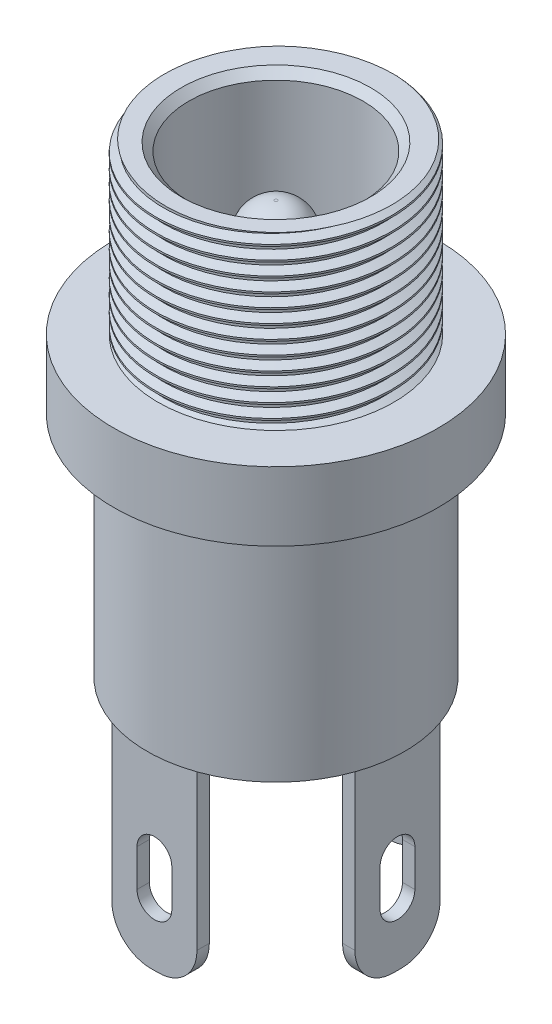
SolidWorks part; units mm, degrees
material "Chrome Stainless Steel"
ref_plane "Front" through (0, 0, 0) normal (0, 0, 1) x (1, 0, 0)
ref_plane "Top" through (0, 0, 0) normal (0, 1, 0) x (1, 0, 0)
ref_plane "Right" through (0, 0, 0) normal (1, 0, 0) x (0, 0, -1)
sketch "Sketch1" plane through (0, 0, 0) normal (0, 1, 0) x (1, 0, 0)
  circle A0 centre (0, 0) radius 3.8735
  circle A1 centre (0, 0) radius 2.8575
  dimension "D1" = 7.747
  dimension "D2" = 5.715
extrude "Boss-Extrude1" add sketch "Sketch1" along normal blind 5.461
chamfer "Chamfer1" distance 0.254 angle 45 1 edges at (0, 5.461, 2.8575)
sketch "Sketch2" plane through (0, 0, 0) normal (0, -1, 0) x (1, 0, 0)
  circle A0 centre (0, 0) radius 5.334
  dimension "D1" = 10.668
extrude "Boss-Extrude2" add sketch "Sketch2" along normal blind 2.2606
sketch "Sketch3" plane through (0, -2.2606, 0) normal (0, -1, 0) x (1, 0, 0)
  circle A0 centre (0, 0) radius 4.2291
  dimension "D1" = 8.4582
extrude "Boss-Extrude3" add sketch "Sketch3" along normal blind 7.493
sketch "Sketch4" plane through (0, 5.461, 0) normal (0, 1, 0) x (1, 0, 0)
  circle A0 centre (0, 0) radius 2.8575
extrude "Cut-Extrude1" cut sketch "Sketch4" against normal blind 11
sketch "Sketch5" plane through (0, -5.539, 0) normal (0, 1, 0) x (1, 0, 0)
  circle A0 centre (0, 0) radius 1.05
  dimension "D1" = 2.1
extrude "Boss-Extrude4" add sketch "Sketch5" along normal offset from surface (9.349 mm away) 1.651 up to face at (0, 5.461, 3.1115)
fillet "Fillet1" radius 1 1 edges at (0, 3.81, 1.05)
sketch "Sketch6" plane through (0, -9.7536, 0) normal (0, -1, 0) x (1, 0, 0)
  line L1 (-1.397, 3.9917) -> (1.397, 3.9917)
  line L2 (-1.397, 3.9917) -> (-1.397, 3.5853)
  line L3 (-1.397, 3.5853) -> (1.397, 3.5853)
  line L4 (1.397, 3.9917) -> (1.397, 3.5853)
  line L5 (3.5853, 1.397) -> (3.9917, 1.397)
  line L6 (3.5853, 1.397) -> (3.5853, -1.397)
  line L7 (3.5853, -1.397) -> (3.9917, -1.397)
  line L8 (3.9917, 1.397) -> (3.9917, -1.397)
  line L9 (1.397, -3.5853) -> (-1.397, -3.5853)
  line L10 (1.397, -3.5853) -> (1.397, -3.9917)
  line L11 (1.397, -3.9917) -> (-1.397, -3.9917)
  line L12 (-1.397, -3.5853) -> (-1.397, -3.9917)
  circle A0 centre (0, 0) radius 4.2291 construction
  circle A1 centre (0, 0) radius 4.2291 construction
  point P21 (0, -3.9917)
  point P23 (0, 3.9917)
  point P24 (3.9917, 0)
  dimension "D1" = 2.794
  dimension "D2" = 0.4064
extrude "Boss-Extrude5" add sketch "Sketch6" along normal blind 6.35
sketch "Sketch7" plane through (0, 0, 0) normal (1, 0, 0) x (0, 0, -1)
  line L0 (0, -12.8651) -> (0, -14.0843) construction
  line L1 (0.5715, -12.8651) -> (0.5715, -14.0843)
  line L2 (-0.5715, -12.8651) -> (-0.5715, -14.0843)
  line L3 (1.397, -16.1036) -> (-1.397, -16.1036) construction
  arc A0 (0.5715, -12.8651) -> (-0.5715, -12.8651) centre (0, -12.8651) ccw
  arc A1 (-0.5715, -14.0843) -> (0.5715, -14.0843) centre (0, -14.0843) ccw
  point P2 (0, -13.4747)
  point P7 (0, -12.2936)
  point P9 (0, -14.6558)
  dimension "D1" = 1.143
  dimension "D2" = 2.3622
  dimension "D3" = 1.4478
extrude "Cut-Extrude2" cut sketch "Sketch7" along normal through all
sketch "Sketch8" plane through (0, 0, 0) normal (0, 0, 1) x (1, 0, 0)
  line L0 (0, -12.8651) -> (0, -14.0843) construction
  line L1 (0.5715, -12.8651) -> (0.5715, -14.0843)
  line L2 (-0.5715, -12.8651) -> (-0.5715, -14.0843)
  arc A0 (0.5715, -12.8651) -> (-0.5715, -12.8651) centre (0, -12.8651) ccw
  arc A1 (-0.5715, -14.0843) -> (0.5715, -14.0843) centre (0, -14.0843) ccw
  point P2 (0, -13.4747)
  dimension "D1" = 1.143
extrude "Cut-Extrude3" cut sketch "Sketch8" against normal through all both and the other way through all
fillet "Fillet2" radius 1.27 6 edges at (3.7885, -16.1036, -1.397) (3.7885, -16.1036, 1.397) (1.397, -16.1036, -3.7885) (-1.397, -16.1036, -3.7885) (-1.397, -16.1036, 3.7885) (1.397, -16.1036, 3.7885)
thread "Thread1" pitch 0.45 method cut profile "Thread Profile1" start angle 0, offset 0.508, length 6.096, pitch 0.45, diameter 7.747
ref_plane "Plane1" through (-3.8735, 5.969, 0) normal (0, 0, 1) x (-1, 0, 0)
sketch "Thread Profile1" plane through (-3.8735, 5.969, 0) normal (0, 0, 1) x (-1, 0, 0)
  line L0 (0, 0) -> (0, 0.45) construction
  line L11 (0, 0) -> (0, 0.3937)
  line L12 (0, 0.3937) -> (-0.2436, 0.2531)
  line L13 (-0.2436, 0.2531) -> (-0.2436, 0.1406)
  line L15 (-0.2436, 0.1406) -> (0, 0)
  line L17 (-0.2436, 0.1969) -> (0, 0.1969) construction
  point P2 (0, 0)
  dimension "Pitch" = 0.45
  dimension "Profile_Angle" = 60
  dimension "Profile_Land" = 0.1125
  dimension "Profile_Height" = 0.2436
